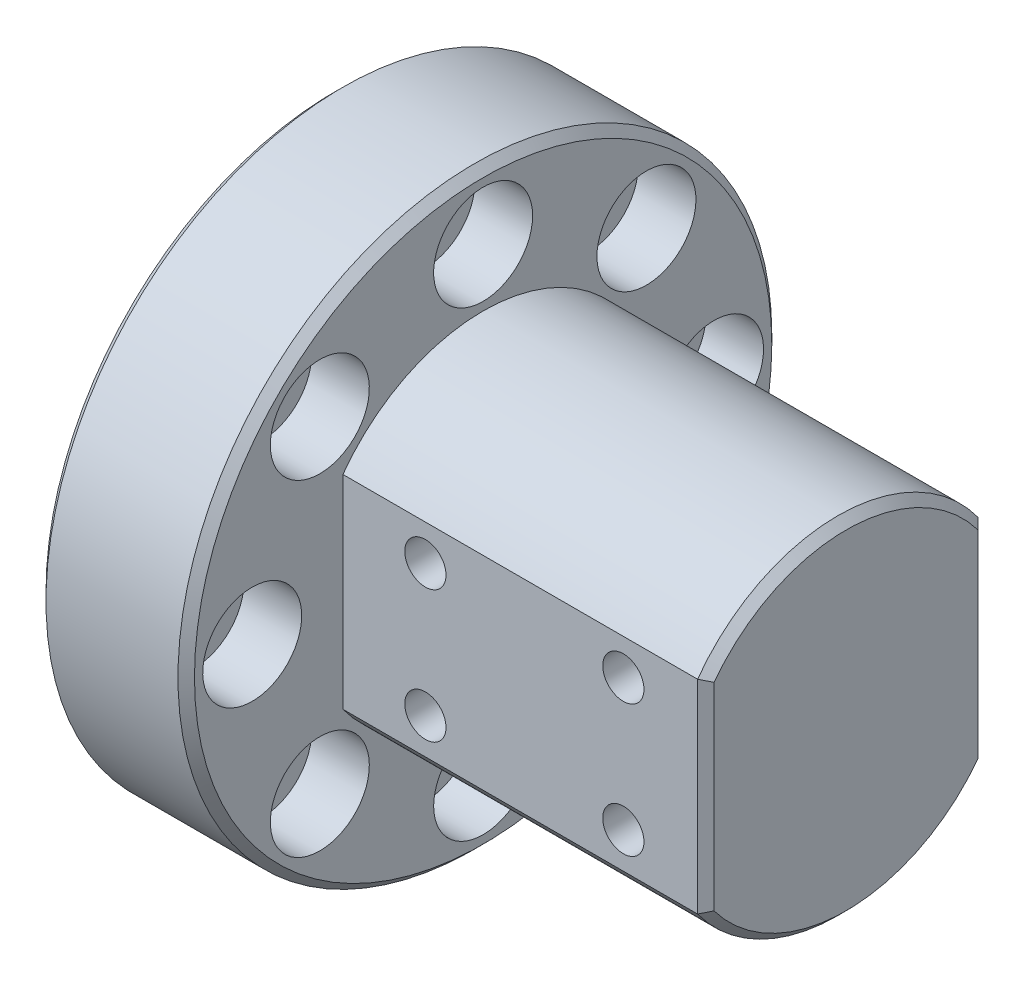
SolidWorks part; units mm, degrees
ref_plane "Front Plane" through (0, 0, 0) normal (0, 0, 1) x (1, 0, 0)
ref_plane "Top Plane" through (0, 0, 0) normal (0, 1, 0) x (1, 0, 0)
ref_plane "Right Plane" through (0, 0, 0) normal (1, 0, 0) x (0, 0, -1)
sketch "Sketch1" plane through (0, 0, 0) normal (1, 0, 0) x (0, 0, -1)
  circle A0 centre (0, 0) radius 18
  dimension "D1" = 36
extrude "Boss-Extrude1" add sketch "Sketch1" along normal blind 9 contours A0
sketch "Sketch2" plane through (9, 0, 0) normal (1, 0, 0) x (0, 0, -1)
  circle A0 centre (0, 0) radius 10.5
  dimension "D1" = 21
extrude "Boss-Extrude2" add sketch "Sketch2" along normal blind 22
sketch "Sketch3" plane through (9, 0, 0) normal (1, 0, 0) x (0, 0, -1)
  circle A0 centre (0, 0) radius 14 construction
  circle A1 centre (0, 14) radius 1.75
  circle A2 centre (0, 14) radius 3
  dimension "D1" = 3.5
  dimension "D2" = 28
  dimension "D3" = 6
extrude "Cut-Extrude2" cut sketch "Sketch3" against normal through all contours A1
extrude "Cut-Extrude3" cut sketch "Sketch3<3>" against normal blind 3.5
sketch "Sketch3<3>" plane through (9, 0, 0) normal (1, 0, 0) x (0, 0, -1) same geometry as "Sketch3"
pattern_circular "CirPattern1" count 8 over 360 about axis through (31, 0, 0) along (-1, 0, 0) of "Cut-Extrude3", "Cut-Extrude2"
chamfer "Chamfer1" distance 0.5 angle 45 2 edges at (9, 0, -18) (0, 0, -18)
sketch "Sketch4" plane through (9, 0, 0) normal (1, 0, 0) x (0, 0, -1)
  line L0 (0, 0) -> (-8.5, 4) construction
  line L1 (-8.5, 6.1644) -> (8.5, 6.1644)
  line L2 (-8.5, 6.1644) -> (-8.5, -6.1644)
  line L3 (-8.5, -6.1644) -> (8.5, -6.1644)
  line L4 (8.5, 6.1644) -> (8.5, -6.1644)
  line L5 (-8.5, 4) -> (-8.5, -4)
  line L6 (-8.5, -4) -> (0, 0) construction
  line L7 (-8.5, 0) -> (0, 0) construction
  circle A1 centre (0, 0) radius 10.5
  circle A2 centre (0, 0) radius 10.5
  circle M22 centre (0, 0) radius 10.5
  dimension "D2" = 8.5
  dimension "D3" = 12.3288
  dimension "D4" = 8
  dimension "D1" = 0
extrude "Cut-Extrude4" cut sketch "Sketch4" along normal through all contours L2 M22 | L4 M22 region at (9, 0, 9.3069) region at (9, 0, -9.3069)
sketch "Sketch5" plane through (0, 0, 8.5) normal (0, 0, 1) x (1, 0, 0)
  line L1 (14, 4) -> (26, 4)
  line L2 (14, 4) -> (14, -4)
  line L3 (14, -4) -> (26, -4)
  line L4 (26, 4) -> (26, -4)
  line L5 (14, 0) -> (0, 0) construction
  line L7 (9, -17.5) -> (9, 17.5) construction
  line L8 (9, -17.5) -> (9, 17.5) construction
  dimension "D1" = 5
  dimension "D2" = 8
  dimension "D3" = 12
hole_wizard "M3 Tapped Hole1" positions "3DSketch1" profile "Sketch7" tap size "M3" standard "ISO" end condition through all
sketch3d "3DSketch1"
  point P0 (14, 4, 8.5)
  point P3 (26, 4, 8.5)
  point P6 (14, -4, 8.5)
  point P9 (26, -4, 8.5)
sketch "Sketch7" plane through (14, 4, 8.5) normal (1, 0, 0) x (0, -1, 0)
  line L0 (0, 0) -> (0, 26.5)
  line L1 (0, 26.5) -> (1.25, 26.5)
  line L2 (1.25, 26.5) -> (1.25, 0)
  line L5 (1.25, 0) -> (0, 0)
  line L11 (0, -6.35) -> (0, 107.95) construction
  dimension "Thru Tap Drill Dia." = 2.5
  dimension "Thru Tap Drill Depth" = 26.5
cosmetic thread "Hole Thread1" parameters "D2"=3
cosmetic thread "Hole Thread2" parameters "D2"=3
cosmetic thread "Hole Thread3" parameters "D2"=3
cosmetic thread "Hole Thread4" parameters "D2"=3
chamfer "Chamfer2" distance 0.5 angle 45 4 edges at (31, 0, -8.5) (31, -10.5, 0) (31, 0, 8.5) (31, 10.5, 0)
